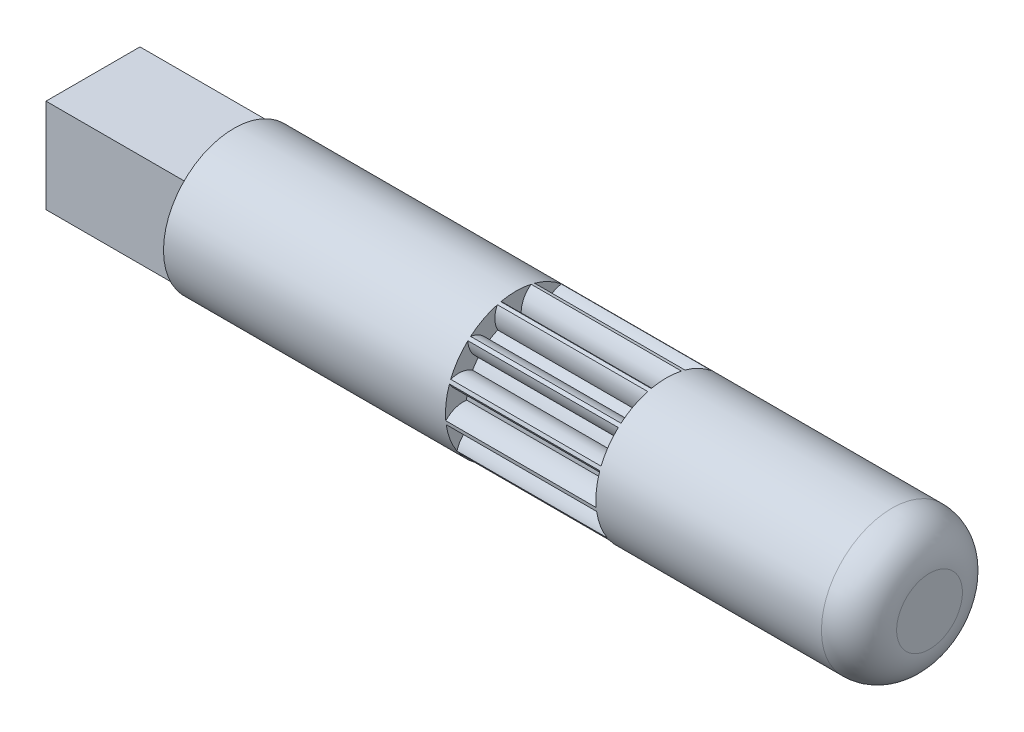
SolidWorks part; units mm, degrees
ref_plane "Plane1" through (0, 0, 0) normal (0, 0, 1) x (1, 0, 0)
ref_plane "Plane2" through (0, 0, 0) normal (0, 1, 0) x (1, 0, 0)
ref_plane "Plane3" through (0, 0, 0) normal (1, 0, 0) x (0, 0, -1)
sketch "HoldingSke" plane through (0, 0, 0) normal (0, 1, 0) x (1, 0, 0)
  line L0 (0, 0) -> (1.9487, -0.4499)
  line L1 (-15, 0) -> (100, 0) construction
  line L2 (0, 0) -> (-2.1039, 2.3779)
  line L3 (0, 0) -> (-11.863, 4.5341)
  line L4 (0, 0) -> (8.4147, 1.9427)
  line L5 (0, 0) -> (-46.8476, -17.4728)
  line L6 (0, 0) -> (-9.9476, -6.7116)
  line L7 (-2.1039, 2.3779) -> (8.6586, 51.2059)
  line L8 (-76.2, 54.61) -> (-76.1, 54.61)
  line L9 (-71.009, 38.7566) -> (-53.1078, 45.2721)
  line L10 (-76.2, 71.12) -> (104.1128, 71.12)
  line L11 (0, 0) -> (-12, 0)
  line L12 (-76.2, 101.6) -> (-76.181, 101.6)
  line L13 (24.9733, 27.94) -> (52.9518, 28.4284)
  line L14 (24.9733, 27.94) -> (24.9743, 27.94)
  line L15 (24.9733, 27.94) -> (100.4006, 29.5858)
  line L16 (-63.627, -0.5) -> (-12.827, -0.5)
  circle A0 centre (0, 0) radius 0.4
  circle A1 centre (0, 0) radius 2.624
  circle A2 centre (0, 0) radius 37.5
  circle A3 centre (0, 0) radius 0.4
  dimension "Num_teeth" = 13
  dimension "Pitch_radius" = 180.3128
  dimension "Width" = 12
sketch "BasProSke" plane through (0, 0, 0) normal (0, 1, 0) x (1, 0, 0)
  line L0 (-10, 0) -> (60, 0) construction
  line L1 (0, 0) -> (0, 3.75)
  line L2 (0, 0) -> (8, 0)
  line L3 (8, 0) -> (8, 3.75)
  line L4 (8, 3.75) -> (0, 3.75)
  dimension "Thickness" = 8
  dimension "Diameter" = 7.5
revolve "Base-Revolve" add sketch "BasProSke" angle 360 about L0
sketch "TooCutSke" plane through (0, 0, 0) normal (1, 0, 0) x (0, 0, -1)
  line L1 (0, 0) -> (0, 107) construction
  line L2 (0, 0) -> (-0.425, 3.2221) construction
  line L3 (0, 0) -> (-1.5461, 6.2726) construction
  line L4 (-0.425, 3.2221) -> (-0.773, 3.1363) construction
  arc A0 (0.2752, 2.6095) -> (-0.2752, 2.6095) centre (0, 0) ccw
  arc A1 (0.8316, 3.6827) -> (-0.8316, 3.6827) centre (0, 0) ccw
  circle A2 centre (0, 0) radius 3.25 construction
  circle A3 centre (0, 0) radius 3.054 construction
  arc A4 (-0.2752, 2.6095) -> (-0.8316, 3.6827) centre (-1.5752, 2.6164) ccw
  arc A5 (0.8316, 3.6827) -> (0.2752, 2.6095) centre (1.5752, 2.6164) ccw
extrude "ToothCut" cut sketch "TooCutSke" along normal through all
fillet "Breaks" [suppressed] radius 0.01 tangent propagation no
fillet "RootFillets" [suppressed] radius 0.126
pattern_circular "TeethCuts" count 13 every 27.692 about axis through (-10, 0, 0) along (1, 0, 0) of "ToothCut", "RootFillets", "Breaks"
sketch "HubNeaOneSke" plane through (0, 0, 0) normal (-1, 0, 0) x (0, 0, 1)
  circle A0 centre (0, 0) radius 2.624
  dimension "Diameter" = 5.248
extrude "HubNearOne" [suppressed] add sketch "HubNeaOneSke" along normal blind 42.0001
sketch "HubNeaBotSke" plane through (0, 0, 0) normal (-1, 0, 0) x (0, 0, 1)
  circle A0 centre (0, 0) radius 2.624
  dimension "Diameter" = 5.248
extrude "HubNearBoth" [suppressed] add sketch "HubNeaBotSke" along normal blind 21
ref_plane "FarPln" through (8, 0, 0) normal (1, 0, 0) x (0, 0, -1)
sketch "HubFarSke" plane through (8, 0, 0) normal (1, 0, 0) x (0, 0, -1)
  circle A0 centre (0, 0) radius 2.624
  dimension "Diameter" = 5.248
extrude "HubFar" [suppressed] add sketch "HubFarSke" along normal blind 21
sketch "BorSke" plane through (0, 0, 0) normal (1, 0, 0) x (0, 0, -1)
  circle A0 centre (0, 0) radius 0.4
  dimension "Diameter" = 0.8
extrude "Bore" cut sketch "BorSke" along normal mid plane 100.0001
sketch "KeySke" plane through (0, 0, 0) normal (1, 0, 0) x (0, 0, -1)
  line L0 (-0.05, 0) -> (-0.05, 0.5)
  line L1 (-0.05, 0.5) -> (0.05, 0.5)
  line L2 (0.05, 0.5) -> (0.05, 0)
  line L3 (0, 0) -> (0, 34) construction
  line L4 (-0.05, 0) -> (0.05, 0)
  dimension "Width" = 0.1
extrude "Keyway" [suppressed] cut sketch "KeySke" along normal mid plane 100.0001
pattern_circular "Keyway2" [suppressed] count 2 every 90 about axis through (-10, 0, 0) along (1, 0, 0) reverse direction yes
sketch "Sketch1" [suppressed] plane through (0, 0, 0) normal (-1, 0, 0) x (0, 0, 1)
  circle A0 centre (0, 0) radius 3
  dimension "D1" = 6
sketch "Sketch3" plane through (0, 0, 0) normal (-1, 0, 0) x (0, 0, 1)
  circle A0 centre (0, 0) radius 3.75
extrude "Boss-Extrude3" add sketch "Sketch3" along normal blind 15
sketch "Sketch4" plane through (-15, 0, 0) normal (-1, 0, 0) x (0, 0, 1)
  line L1 (-2.5, 2.5) -> (2.5, 2.5)
  line L2 (-2.5, 2.5) -> (-2.5, -2.5)
  line L3 (-2.5, -2.5) -> (2.5, -2.5)
  line L4 (2.5, 2.5) -> (2.5, -2.5)
  line L5 (-2.5, 2.5) -> (2.5, -2.5) construction
  line L6 (-2.5, -2.5) -> (2.5, 2.5) construction
  point P0 (0, 0)
  dimension "D1" = 5
  dimension "D2" = 5
extrude "Boss-Extrude4" add sketch "Sketch4" along normal blind 7.5
sketch "Sketch5" plane through (8, 0, 0) normal (1, 0, 0) x (0, 0, -1)
  circle A0 centre (0, 0) radius 3.75
extrude "Boss-Extrude5" add sketch "Sketch5" along normal blind 14
fillet "Fillet1" radius 2 1 edges at (22, 0, -3.75)
sketch "Sketch7" [suppressed] plane through (8, 0, 0) normal (1, 0, 0) x (0, 0, -1)
  circle A0 centre (0, 0) radius 0.4
extrude "Boss-Extrude7" [suppressed] add sketch "Sketch7" against normal blind 10
ref_axis "Axis2" through (-80.9, 0, 0) along (1, 0, 0)
sketch "Sketch8" plane through (22, 0, 0) normal (1, 0, 0) x (0, 0, -1)
  circle A0 centre (0, 0) radius 1.3033
extrude "Boss-Extrude8" add sketch "Sketch8" against normal blind 30
equation "' \"Module@HoldingSke\" = 6.35"
equation "' \"Num_teeth@HoldingSke\" = 12"
equation "' \"Ap@HoldingSke\" =  20"
equation "' \"Ap@HoldingSke\" = 20"
equation "' \"Width@HoldingSke\" = 0.5 * 25.4"
equation "' \"Hub_dia@HoldingSke\"= 1 * 25.4"
equation "' \"Hub_dia@HoldingSke\" = 1 * 25.4"
equation "' \"Overall_len@HoldingSke\" = 1.0 * 25.4"
equation "' \"Bore@HoldingSke\" = 0.75 * 25.4"
equation "' \"T_dim@HoldingSke\" = 0.1 * 25.4"
equation "' \"Width@KeySke\" = 0.25 * 25.4"
equation "' \"Show_teeth@HoldingSke\" = 13"
equation "' \"Backlash@HoldingSke\" = 0.009 * 25.4"
equation "' \"Addendum_fac@HoldingSke\" = 1.0"
equation "' \"Dedendum_fac@HoldingSke\" = 1.25"
equation "' \"Dedendum_add@HoldingSke\" = 0.00005 * 25.4"
equation "' \"Clearance_fac@HoldingSke\" = 0.25"
equation "\"Pitch@HoldingSke\" = 1 / \"Module@HoldingSke\""
equation "\"Overcut_dia@TooCutSke\" = (\"Num_teeth@HoldingSke\" + 2 * \"Addendum_fac@HoldingSke\") / \"Pitch@HoldingSke\" + 0.002 * 25.4"
equation "\"Pitch_dia@TooCutSke\" = \"Num_teeth@HoldingSke\" / \"Pitch@HoldingSke\""
equation "\"Base_dia@TooCutSke\" = \"Num_teeth@HoldingSke\" / \"Pitch@HoldingSke\" * cos((\"Ap@HoldingSke\"  * 3.14159265 / 180))"
equation "\"Root_dia@TooCutSke\" = (\"Num_teeth@HoldingSke\" + 2) / \"Pitch@HoldingSke\" - 2 * (\"Addendum_fac@HoldingSke\" + \"Dedendum_fac@HoldingSke\") / \"Pitch@HoldingSke\" - \"Dedendum_add@HoldingSke\" * 2"
equation "\"Half_ang@TooCutSke\" = 180 / \"Num_teeth@HoldingSke\""
equation "\"Half_CT@TooCutSke\" = \"Num_teeth@HoldingSke\" / \"Pitch@HoldingSke\" * sin((3.14159265 / 2 / \"Num_teeth@HoldingSke\")) / 2 - 7 * \"Backlash@HoldingSke\" / 4"
equation "\"Flank_rad@TooCutSke\" = \"Num_teeth@HoldingSke\" / \"Pitch@HoldingSke\" / 5"
equation "\"Radius@RootFillets\" = \"Clearance_fac@HoldingSke\" / \"Pitch@HoldingSke\" + \"Dedendum_add@HoldingSke\""
equation "\"Break_rad@Breaks\" = 0.02 / \"Pitch@HoldingSke\""
equation "\"Thickness@HoldingSke\" = \"Width@HoldingSke\""
equation "\"OAL@HoldingSke\" = \"Thickness@HoldingSke\""
equation "\"MHD@HoldingSke\" = (\"Num_teeth@HoldingSke\" + 2) / \"Pitch@HoldingSke\" - 2 * (\"Addendum_fac@HoldingSke\" + \"Dedendum_fac@HoldingSke\")  / \"Pitch@HoldingSke\" - \"Dedendum_add@HoldingSke\" * 2"
equation "\"MBD@HoldingSke\" = (\"Num_teeth@HoldingSke\" + 2) / \"Pitch@HoldingSke\" - 2 * (\"Addendum_fac@HoldingSke\" + \"Dedendum_fac@HoldingSke\")  / \"Pitch@HoldingSke\" - \"Dedendum_add@HoldingSke\" * 2 - 0.002 * 25.4"
equation "\"MHD@HoldingSke\" = ((sgn( \"MHD@HoldingSke\" - \"Hub_dia@HoldingSke\" )-1)*( \"MHD@HoldingSke\" - \"Hub_dia@HoldingSke\" ))/-2+ \"Hub_dia@HoldingSke\""
equation "\"MBD@HoldingSke\" = ((sgn( \"MBD@HoldingSke\" - \"Bore@HoldingSke\" )-1)*( \"MBD@HoldingSke\" - \"Bore@HoldingSke\" ))/-2+ \"Bore@HoldingSke\""
equation "\"OAL@HoldingSke\" = ((sgn( \"OAL@HoldingSke\" - \"Overall_len@HoldingSke\" )+1)*( \"OAL@HoldingSke\" - \"Overall_len@HoldingSke\" ))/2 + \"Overall_len@HoldingSke\" + 0.000002 * 25.4"
equation "\"Num_teeth@TeethCuts\" = int( \"Show_teeth@HoldingSke\" ) + 1"
equation "\"Num_teeth@TeethCuts\" = ((sgn( \"Num_teeth@TeethCuts\" - \"Num_teeth@HoldingSke\" )-1)*( \"Num_teeth@TeethCuts\" - \"Num_teeth@HoldingSke\" ))/-2+ \"Num_teeth@HoldingSke\""
equation "\"Num_teeth@TeethCuts\" = ((sgn( \"Num_teeth@TeethCuts\" - 2.0)+1)*( \"Num_teeth@TeethCuts\" - 2.0))/2 +2.0"
equation "\"Angle@TeethCuts\" = 360.0 / \"Num_teeth@HoldingSke\""
equation "\"Diameter@BasProSke\" = (\"Num_teeth@HoldingSke\" + 2 * \"Addendum_fac@HoldingSke\") / \"Pitch@HoldingSke\""
equation "\"Thickness@BasProSke\"=8"
equation "' \"Fillet_rad@BasProSke\" =  \"Thickness@HoldingSke\" * 0.05"
equation "' \"Fillet_rad@BasProSke\" = \"Thickness@HoldingSke\" * 0.05"
equation "\"MHD@HoldingSke\" = ((sgn( \"MHD@HoldingSke\" - \"Root_dia@TooCutSke\" )-1)*( \"MHD@HoldingSke\" - \"Root_dia@TooCutSke\" ))/-2+ \"Root_dia@TooCutSke\""
equation "\"Diameter@HubNeaOneSke\" = \"MHD@HoldingSke\""
equation "\"Length@HubNearOne\" = \"OAL@HoldingSke\" - \"Thickness@BasProSke\""
equation "\"Diameter@HubNeaBotSke\" = \"MHD@HoldingSke\""
equation "\"Length@HubNearBoth\" = ( \"OAL@HoldingSke\" - \"Thickness@BasProSke\" ) / 2.0"
equation "\"Thickness@FarPln\" = \"Thickness@BasProSke\""
equation "\"Diameter@HubFarSke\" = \"MHD@HoldingSke\""
equation "\"Length@HubFar\" = ( \"OAL@HoldingSke\" - \"Thickness@BasProSke\" ) / 2.0"
equation "\"Diameter@BorSke\" = \"MBD@HoldingSke\""
equation "\"D1@Bore\" = \"OAL@HoldingSke\" * 2.0"
equation "\"D1@Keyway\" = \"OAL@HoldingSke\" * 2.0"
equation "\"Offset@KeySke\" = \"T_dim@HoldingSke\" + \"MBD@HoldingSke\" / 2.0"
